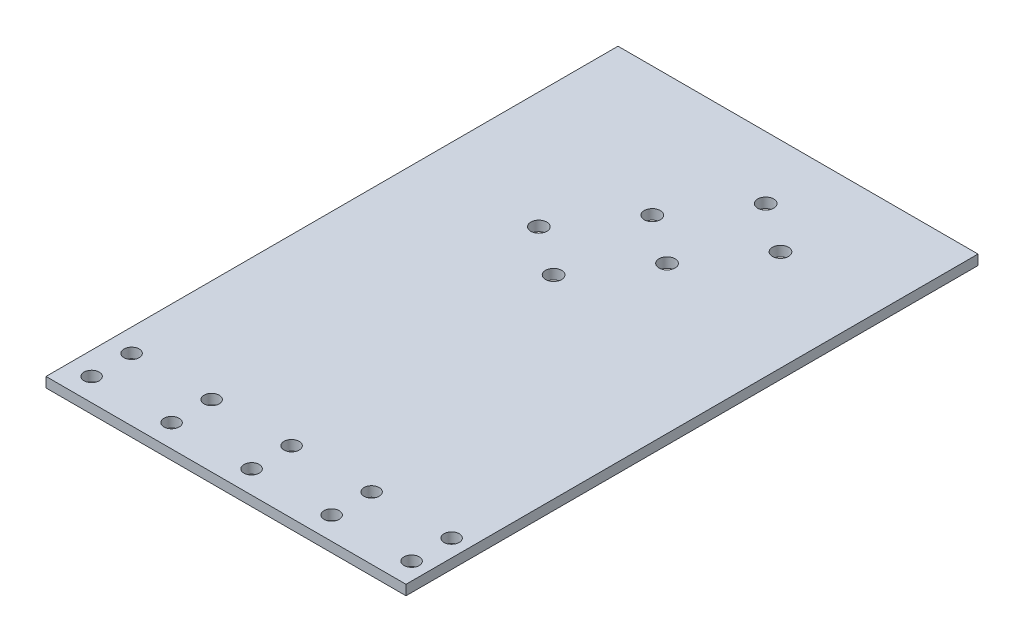
SolidWorks part; units mm, degrees
material "6061-T6 (SS)"
ref_plane "Front Plane" through (0, 0, 0) normal (0, 0, 1) x (1, 0, 0)
ref_plane "Top Plane" through (0, 0, 0) normal (0, 1, 0) x (1, 0, 0)
ref_plane "Right Plane" through (0, 0, 0) normal (1, 0, 0) x (0, 0, -1)
sketch "Sketch1" plane through (0, 0, 0) normal (0, 1, 0) x (1, 0, 0)
  line L5 (0, 0) -> (114.3, 0)
  line L6 (0, 0) -> (0, 181.61)
  line L7 (0, 181.61) -> (114.3, 181.61)
  line L8 (114.3, 0) -> (114.3, 181.61)
  dimension "D1" = 181.61
  dimension "D2" = 114.3
extrude "Boss-Extrude1" add sketch "Sketch1" along normal blind 3.175
sketch "Sketch2" plane through (0, 3.175, 0) normal (0, 1, 0) x (1, 0, 0)
  line L0 (0, 0) -> (114.3, 0) construction
  line L1 (0, 181.61) -> (0, 0) construction
  circle A0 centre (7.239, 7.239) radius 2.413
  circle A2 centre (7.239, 19.939) radius 2.413
  circle A3 centre (32.639, 19.939) radius 2.413
  circle A4 centre (58.039, 19.939) radius 2.413
  circle A5 centre (83.439, 19.939) radius 2.413
  circle A6 centre (108.839, 19.939) radius 2.413
  circle A7 centre (32.639, 7.239) radius 2.413
  circle A8 centre (58.039, 7.239) radius 2.413
  circle A9 centre (83.439, 7.239) radius 2.413
  circle A10 centre (108.839, 7.239) radius 2.413
  dimension "D1" = 4.826
  dimension "D2" = 7.239
  dimension "D3" = 7.239
  dimension "D4" = 2
  dimension "D5" = 5
extrude "Cut-Extrude1" cut sketch "Sketch2" against normal through all
sketch "Sketch3" plane through (0, 0, 0) normal (0, -1, 0) x (1, 0, 0)
  line L10 (37.07, -119.4115) -> (66.7351, -161.7776) construction
  line L11 (37.07, -119.4115) -> (52.6748, -108.4849) construction
  line L12 (66.7351, -161.7776) -> (82.3399, -150.851) construction
  line L13 (52.6748, -108.4849) -> (82.3399, -150.851) construction
  line L14 (0, -1.7463) -> (0, 1.7463) construction
  circle A14 centre (37.07, -119.4115) radius 2.5527
  circle A15 centre (52.6748, -108.4849) radius 2.5527
  circle A16 centre (82.3399, -150.851) radius 2.5527
  circle A17 centre (66.7351, -161.7776) radius 2.5527
  circle A18 centre (51.9025, -140.5946) radius 2.5527
  circle A19 centre (67.5074, -129.6679) radius 2.5527
  point P14 (83.284, -152.1993)
  dimension "D4" = 19.05
  dimension "D5" = 108.4849
  dimension "D2" = 5.1054
  dimension "D1" = 35
  dimension "D6" = 52.6748
  dimension "D3" = 25.8597
extrude "Cut-Extrude2" cut sketch "Sketch3" against normal through all
sketch "Sketch4" plane through (0, 0, 0) normal (0, -1, 0) x (1, 0, 0)
  line L0 (64.8638, -172.3902) -> (30.1383, -122.7972)
  line L2 (114.3, -181.61) -> (0, -181.61)
  line L3 (0, -181.61) -> (0, -24.617)
  line L5 (114.3, -30.5457) -> (89.2092, -155.3434)
  line L6 (114.3, 0) -> (114.3, -181.61) construction
  line L7 (114.3, -30.5457) -> (114.3, -181.61)
  line L9 (37.07, -119.4115) -> (66.7351, -161.7776) construction
  line L10 (66.7351, -161.7776) -> (82.3399, -150.851) construction
  line L11 (64.8638, -172.3902) -> (89.2092, -155.3434)
  line L12 (30.1383, -122.7972) -> (0, -24.617)
  line L13 (0, -1.7463) -> (0, 1.7463) construction
  circle A0 centre (82.3399, -150.851) radius 2.5527 construction
  circle A1 centre (66.7351, -161.7776) radius 2.5527 construction
  circle A2 centre (37.07, -119.4115) radius 2.5527 construction
  circle A3 centre (82.3399, -150.851) radius 2.5527 construction
  circle A4 centre (66.7351, -161.7776) radius 2.5527 construction
  circle A5 centre (37.07, -119.4115) radius 2.5527 construction
  circle A6 centre (108.839, -19.939) radius 2.413 construction
  circle A7 centre (7.239, -19.939) radius 2.413 construction
  circle A8 centre (108.839, -19.939) radius 2.413 construction
  circle A9 centre (7.239, -19.939) radius 2.413 construction
  dimension "D1" = 7.62
  dimension "D2" = 7.62
  dimension "D3" = 7.62
  dimension "D4" = 7.62
